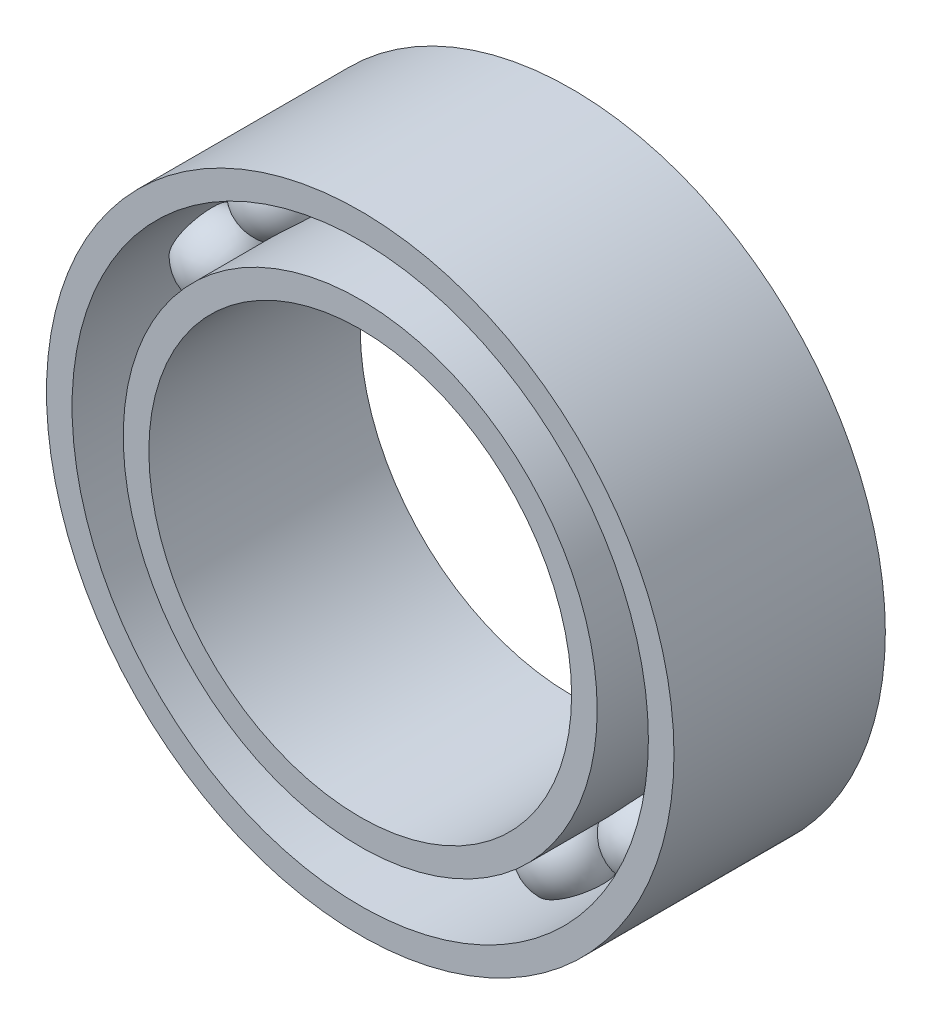
SolidWorks part; units mm, degrees
ref_plane "Front Plane" through (0, 0, 0) normal (0, 0, 1) x (1, 0, 0)
ref_plane "Top Plane" through (0, 0, 0) normal (0, 1, 0) x (1, 0, 0)
ref_plane "Right Plane" through (0, 0, 0) normal (1, 0, 0) x (0, 0, -1)
sketch "Sketch1" plane through (0, 0, 0) normal (0, 0, 1) x (1, 0, 0)
  line L0 (0, 0) -> (3.2, 0) construction
  line L1 (3.2, 0) -> (4.75, 0) construction
  line L2 (0, 0) -> (0, 3.2) construction
  line L3 (0, 3.2) -> (0, 3.975) construction
  line L4 (0, 3.975) -> (0, 4.75) construction
  circle A0 centre (0, 0) radius 4.75
  circle A1 centre (0, 0) radius 3.2
  circle A2 centre (0, 0) radius 3.5875 construction
  circle A3 centre (0, 0) radius 4.3625 construction
  circle A4 centre (0, 0) radius 3.975 construction
  point P7 (3.975, 0)
  point P13 (0, 4.3625)
  point P14 (0, 3.5875)
  dimension "D1" = 6.4
  dimension "D2" = 9.5
extrude "Boss-Extrude1" add sketch "Sketch1" along normal blind 3.2
sketch "Sketch2" plane through (0, 0, 0) normal (0, 0, 1) x (1, 0, 0)
  circle A0 centre (0, 0) radius 3.5875
  circle A1 centre (0, 0) radius 4.3625
  circle A2 centre (0, 0) radius 3.5875 construction
  circle A3 centre (0, 0) radius 4.3625 construction
extrude "Cut-Extrude1" cut sketch "Sketch2" along normal up to next
sketch "Sketch3" plane through (0, 0, 0) normal (1, 0, 0) x (0, 0, -1)
  line L1 (0, 3.975) -> (-3.2, 3.975) construction
  line L2 (0, 3.2) -> (0, 3.975) construction
  line L3 (-3.2, 4.75) -> (-3.2, -4.75) construction
  line L4 (-1.6, 4.5562) -> (-1.6, 3.3938)
  line L5 (-1.6, 3.2) -> (-1.6, 3.5875) construction
  line L6 (0, 3.2) -> (-3.2, 3.2) construction
  line L7 (0, 3.5875) -> (-3.2, 3.5875) construction
  arc A0 (-1.6, 3.3938) -> (-1.6, 4.5562) centre (-1.6, 3.975) ccw
  point P9 (-1.6, 3.975)
  point P11 (-1.6, 3.975)
  point P18 (-1.6, 3.3938)
revolve "Revolve1" add sketch "Sketch3" angle 360 about L4
ref_axis "Axis1" through (0, 0, -0.2) along (0, 0, 1)
pattern_circular "CirPattern1" count 16 over 360 about axis through (0, 0, -0.2) along (0, 0, 1) of "Revolve1"
